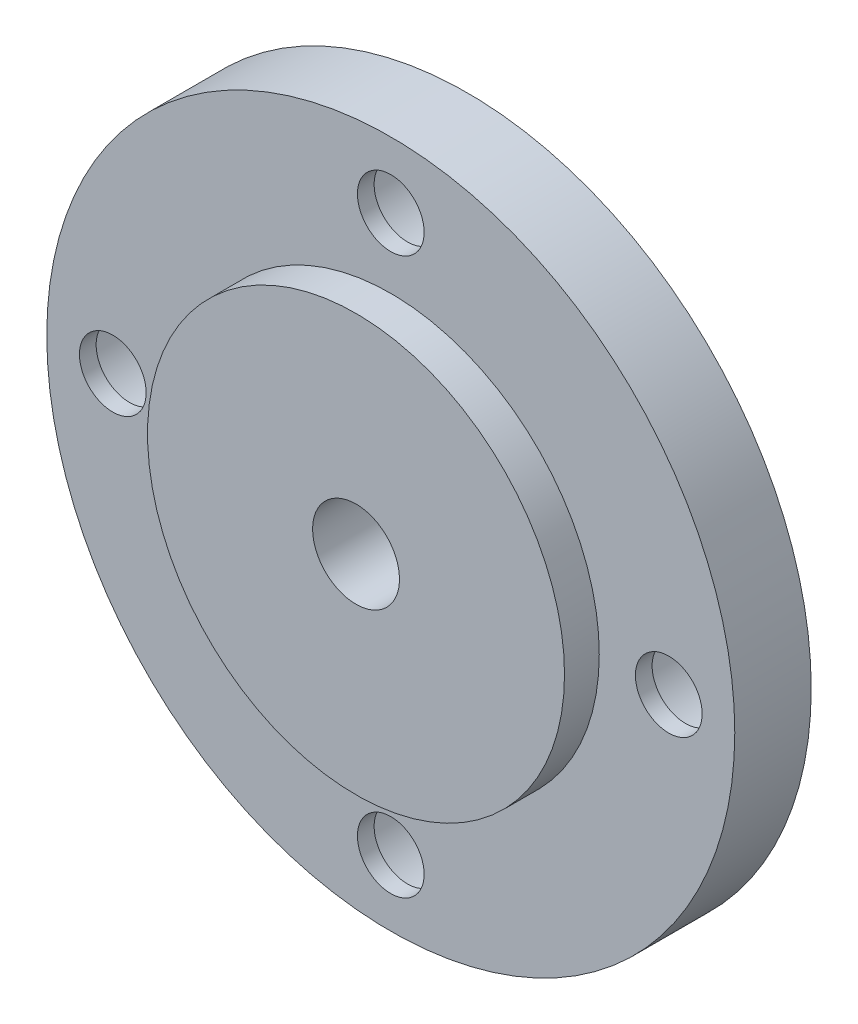
SolidWorks part; units mm, degrees
ref_plane "Front Plane" through (0, 0, 0) normal (0, 0, 1) x (1, 0, 0)
ref_plane "Top Plane" through (0, 0, 0) normal (0, 1, 0) x (1, 0, 0)
ref_plane "Right Plane" through (0, 0, 0) normal (1, 0, 0) x (0, 0, -1)
sketch "Sketch1" plane through (0, 0, 0) normal (0, 0, 1) x (1, 0, 0)
  circle A0 centre (0, 0) radius 12.573
  dimension "D1" = 25.146
extrude "Boss-Extrude1" add sketch "Sketch1" along normal blind 2.794
sketch "Sketch2" plane through (0, 0, 2.794) normal (0, 0, 1) x (1, 0, 0)
  circle A0 centre (0, 0) radius 7.62
  dimension "D1" = 15.24
ref_plane "Plane1" through (0, 0, -4.826) normal (0, 0, 1) x (1, 0, 0)
extrude "Boss-Extrude2" add sketch "Sketch2" along normal blind 1.27 contours A0
sketch "Sketch17" plane through (0, 0, 0) normal (0, 0, -1) x (-1, 0, 0)
  circle A0 centre (0, 0) radius 10.16 construction
  point P3 (10.16, 0)
  dimension "D1" = 20.32
hole_wizard "CBORE for #2 Socket Head Cap Screw1" positions "Sketch19" profile "Sketch18" counterbore size "#2" standard "ANSI Inch"
sketch "Sketch19" plane through (0, 0, 0) normal (0, 0, -1) x (-1, 0, 0)
  point P0 (10.16, 0)
sketch "Sketch18" plane through (-10.16, 0, 0) normal (1, 0, 0) x (0, 1, 0)
  line L0 (0, 0) -> (0, 8.4465)
  line L1 (0, 8.4465) -> (1.2192, 7.714)
  line L2 (1.2192, 7.714) -> (1.2192, 2.1844)
  line L3 (1.2192, 2.1844) -> (2.3812, 2.1844)
  line L4 (2.3812, 2.1844) -> (2.3812, 0)
  line L5 (2.3812, 0) -> (0, 0)
  line L10 (0, 8.4465) -> (-1.2192, 7.714) construction
  line L11 (0, -6.35) -> (0, 107.95) construction
  dimension "Hole Dia." = 2.4384
  dimension "Hole Depth" = 7.714
  dimension "C'Bore Dia." = 4.7625
  dimension "C'Bore Depth" = 2.1844
  dimension "Drill Angle" = 118
ref_axis "Axis2" through (0, 0, 0) along (0, 0, -1)
pattern_circular "CirPattern2" count 4 every 90 about axis through (0, 0, 0) along (0, 0, -1) of "CBORE for #2 Socket Head Cap Screw1"
hole_wizard "1/8 (0.1250) Dowel Hole2" positions "Sketch21" profile "Sketch22" hole size "1/8" standard "ANSI Inch" end condition through all
sketch "Sketch21" plane through (0, 0, 0) normal (0, 0, -1) x (-1, 0, 0)
  point P0 (0, 0)
sketch "Sketch22" plane through (0, 0, 0) normal (1, 0, 0) x (0, 1, 0)
  line L0 (0, 0) -> (0, 4.064)
  line L1 (0, 4.064) -> (1.5875, 4.064)
  line L2 (1.5875, 4.064) -> (1.5875, 0)
  line L5 (1.5875, 0) -> (0, 0)
  line L11 (0, -6.35) -> (0, 107.95) construction
  dimension "Thru Hole Dia." = 3.175
  dimension "Thru Hole Depth" = 4.064
